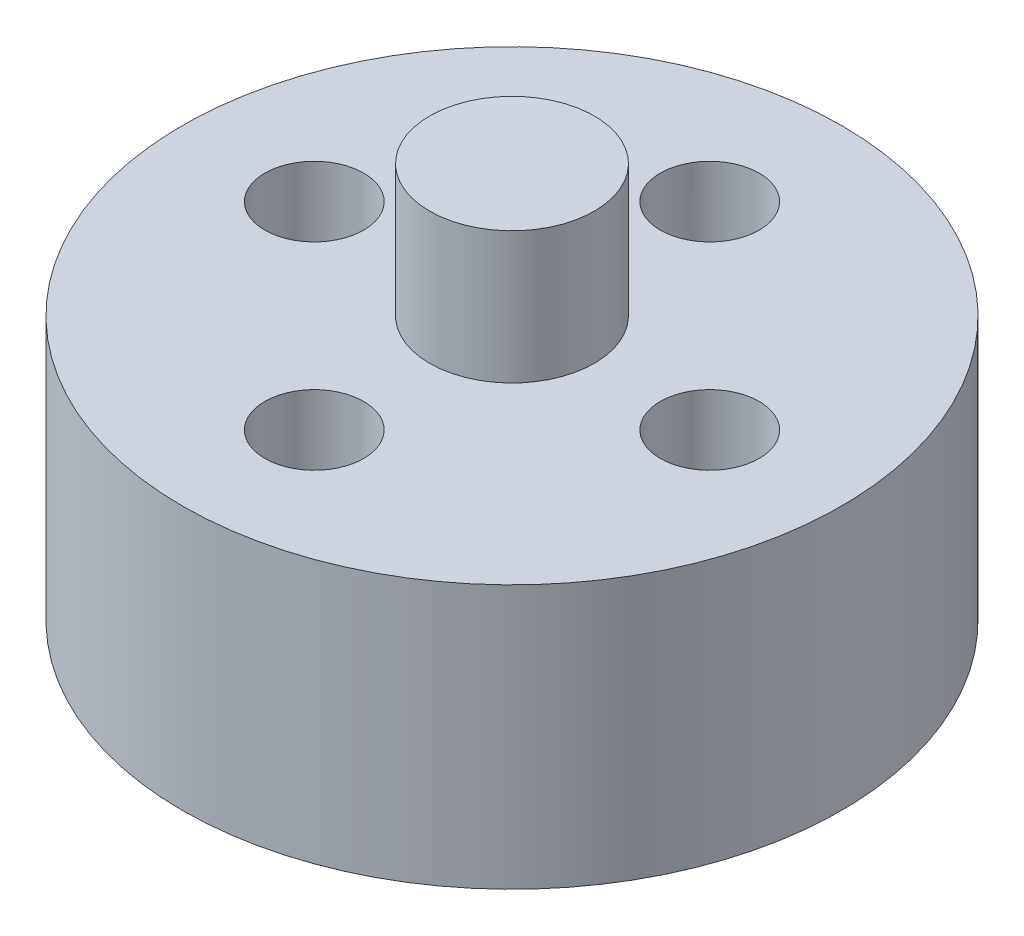
SolidWorks part; units mm, degrees
ref_plane "Front Plane" through (0, 0, 0) normal (0, 0, 1) x (1, 0, 0)
ref_plane "Top Plane" through (0, 0, 0) normal (0, 1, 0) x (1, 0, 0)
ref_plane "Right Plane" through (0, 0, 0) normal (1, 0, 0) x (0, 0, -1)
sketch "Sketch1" plane through (0, 0, 0) normal (0, 1, 0) x (1, 0, 0)
  line L0 (-1.3229, 1.5) -> (1.3229, 1.5)
  arc A0 (-1.3229, 1.5) -> (1.3229, 1.5) centre (0, 0) ccw
  circle A1 centre (0, 0) radius 10
  dimension "D1" = 4
  dimension "D2" = 3.5
  dimension "D3" = 20
extrude "Boss-Extrude1" add sketch "Sketch1" along normal blind 7
sketch "Sketch2" plane through (0, 7, 0) normal (0, 1, 0) x (1, 0, 0)
  circle A1 centre (0, 0) radius 10
  circle A2 centre (0, 0) radius 10
  dimension "D1" = 0
extrude "Boss-Extrude2" add sketch "Sketch2" along normal blind 1
sketch "Sketch3" plane through (0, 8, 0) normal (0, 1, 0) x (1, 0, 0)
  circle A0 centre (0, 0) radius 2.5
  dimension "D1" = 5
extrude "Boss-Extrude3" add sketch "Sketch3" along normal blind 4
sketch "Sketch4" plane through (0, 8, 0) normal (0, 1, 0) x (1, 0, 0)
  circle A0 centre (6, 0) radius 1.5
  circle A1 centre (0, -6) radius 1.5
  circle A2 centre (-6, 0) radius 1.5
  circle A3 centre (0, 6) radius 1.5
  point P12 (0, 0)
  dimension "D1" = 3
  dimension "D2" = 6
  dimension "D3" = 4
extrude "Cut-Extrude1" cut sketch "Sketch4" against normal blind 4
sketch "Sketch5" plane through (0, 0, -1.5) normal (0, 0, 1) x (1, 0, 0)
  line L0 (1.3229, 0) -> (-1.3229, 0) construction
  circle A0 centre (0, 3) radius 1.4
  dimension "D1" = 2.8
  dimension "D2" = 3
extrude "Cut-Extrude2" cut sketch "Sketch5" against normal through all and the other way blind 2
